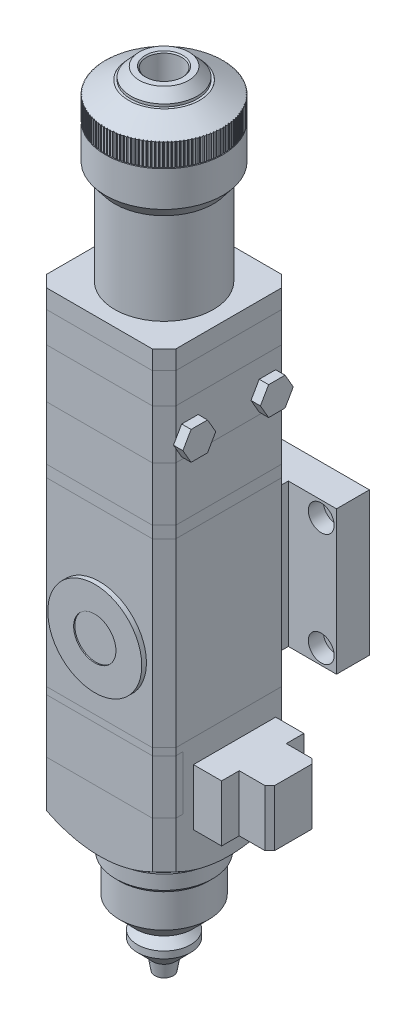
SolidWorks part; units mm, degrees
ref_plane "Front Plane" through (0, 0, 0) normal (0, 0, 1) x (1, 0, 0)
ref_plane "Top Plane" through (0, 0, 0) normal (0, 1, 0) x (1, 0, 0)
ref_plane "Right Plane" through (0, 0, 0) normal (1, 0, 0) x (0, 0, -1)
sketch "Sketch1" plane through (0, 0, 0) normal (0, 1, 0) x (1, 0, 0)
  line L0 (-27.5, 0) -> (27.5, 0) construction
  line L5 (-66.7299, 27.2787) -> (115.2701, 27.2787) construction
  dimension "D1" = 55
sketch "Sketch2" plane through (0, 0, 0) normal (0, 1, 0) x (1, 0, 0)
  line L1 (-27.5, -27.5) -> (27.5, -27.5)
  line L2 (-27.5, -27.5) -> (-27.5, 27.5)
  line L3 (-27.5, 27.5) -> (27.5, 27.5)
  line L4 (27.5, -27.5) -> (27.5, 27.5)
  line L5 (-27.5, -27.5) -> (27.5, 27.5) construction
  line L6 (-27.5, 27.5) -> (27.5, -27.5) construction
  point P0 (0, 0)
  dimension "D1" = 55
sketch "Sketch3" plane through (0, 0, 0) normal (0, 0, 1) x (1, 0, 0)
  line L0 (-51.0962, -28.8167) -> (190.9038, -28.8167) construction
sketch "Sketch33" plane through (0, 0, 0) normal (1, 0, 0) x (0, 0, -1)
  line L0 (-62.9213, -37.0491) -> (115.0787, -37.0491) construction
extrude "Boss-Extrude1" add sketch "Sketch2" against normal blind 8
chamfer "Chamfer1" distance 5 angle 45 4 edges at (27.5, -4, 27.5) (-27.5, -4, -27.5) (-27.5, -4, 27.5) (27.5, -4, -27.5)
sketch "Sketch4" plane through (0, -8, 0) normal (0, -1, 0) x (1, 0, 0)
  line L4 (27.5, -22.5) -> (27.5, 22.5)
  line L5 (22.5, 27.5) -> (-22.5, 27.5)
  line L6 (-27.5, 22.5) -> (-27.5, -22.5)
  line L7 (-22.5, -27.5) -> (22.5, -27.5)
  line L8 (27.5, -22.5) -> (27.5, 22.5)
  line L9 (22.5, 27.5) -> (-22.5, 27.5)
  line L10 (-27.5, 22.5) -> (-27.5, -22.5)
  line L11 (-22.5, -27.5) -> (22.5, -27.5)
  line L16 (-27.5, -22.5) -> (-22.5, -27.5)
  line L17 (-27.5, -22.5) -> (-22.5, -27.5)
  line L18 (22.5, -27.5) -> (27.5, -22.5)
  line L19 (22.5, -27.5) -> (27.5, -22.5)
  line L20 (27.5, 22.5) -> (22.5, 27.5)
  line L21 (27.5, 22.5) -> (22.5, 27.5)
  line L22 (-22.5, 27.5) -> (-27.5, 22.5)
  line L23 (-22.5, 27.5) -> (-27.5, 22.5)
  dimension "D1" = 0
extrude "Boss-Extrude2" add sketch "Sketch4" along normal blind 13 separate body
sketch "Sketch5" plane through (0, -21, 0) normal (0, -1, 0) x (1, 0, 0)
  line L4 (-22.5, -27.5) -> (22.5, -27.5)
  line L5 (27.5, -22.5) -> (27.5, 22.5)
  line L6 (22.5, 27.5) -> (-22.5, 27.5)
  line L7 (-27.5, 22.5) -> (-27.5, -22.5)
  line L8 (-22.5, -27.5) -> (22.5, -27.5)
  line L9 (27.5, -22.5) -> (27.5, 22.5)
  line L10 (22.5, 27.5) -> (-22.5, 27.5)
  line L11 (-27.5, 22.5) -> (-27.5, -22.5)
  line L16 (27.5, 22.5) -> (22.5, 27.5)
  line L17 (27.5, 22.5) -> (22.5, 27.5)
  line L18 (-22.5, 27.5) -> (-27.5, 22.5)
  line L19 (-22.5, 27.5) -> (-27.5, 22.5)
  line L20 (-27.5, -22.5) -> (-22.5, -27.5)
  line L21 (-27.5, -22.5) -> (-22.5, -27.5)
  line L22 (22.5, -27.5) -> (27.5, -22.5)
  line L23 (22.5, -27.5) -> (27.5, -22.5)
  dimension "D1" = 0
extrude "Boss-Extrude3" add sketch "Sketch5" along normal blind 21 separate body
sketch "Sketch6" plane through (0, -42, 0) normal (0, -1, 0) x (1, 0, 0)
  line L4 (-27.5, 22.5) -> (-27.5, -22.5)
  line L5 (-22.5, -27.5) -> (22.5, -27.5)
  line L6 (27.5, -22.5) -> (27.5, 22.5)
  line L7 (22.5, 27.5) -> (-22.5, 27.5)
  line L8 (-27.5, 22.5) -> (-27.5, -22.5)
  line L9 (-22.5, -27.5) -> (22.5, -27.5)
  line L10 (27.5, -22.5) -> (27.5, 22.5)
  line L11 (22.5, 27.5) -> (-22.5, 27.5)
  line L16 (22.5, -27.5) -> (27.5, -22.5)
  line L17 (22.5, -27.5) -> (27.5, -22.5)
  line L18 (27.5, 22.5) -> (22.5, 27.5)
  line L19 (27.5, 22.5) -> (22.5, 27.5)
  line L20 (-22.5, 27.5) -> (-27.5, 22.5)
  line L21 (-22.5, 27.5) -> (-27.5, 22.5)
  line L22 (-27.5, -22.5) -> (-22.5, -27.5)
  line L23 (-27.5, -22.5) -> (-22.5, -27.5)
  dimension "D1" = 0
extrude "Boss-Extrude4" add sketch "Sketch6" along normal blind 23 separate body
sketch "Sketch7" plane through (0, -65, 0) normal (0, -1, 0) x (1, 0, 0)
  line L4 (22.5, 27.5) -> (-22.5, 27.5)
  line L5 (-27.5, 22.5) -> (-27.5, -22.5)
  line L6 (-22.5, -27.5) -> (22.5, -27.5)
  line L7 (27.5, -22.5) -> (27.5, 22.5)
  line L8 (22.5, 27.5) -> (-22.5, 27.5)
  line L9 (-27.5, 22.5) -> (-27.5, -22.5)
  line L10 (-22.5, -27.5) -> (22.5, -27.5)
  line L11 (27.5, -22.5) -> (27.5, 22.5)
  line L16 (-27.5, -22.5) -> (-22.5, -27.5)
  line L17 (-27.5, -22.5) -> (-22.5, -27.5)
  line L18 (22.5, -27.5) -> (27.5, -22.5)
  line L19 (22.5, -27.5) -> (27.5, -22.5)
  line L20 (27.5, 22.5) -> (22.5, 27.5)
  line L21 (27.5, 22.5) -> (22.5, 27.5)
  line L22 (-22.5, 27.5) -> (-27.5, 22.5)
  line L23 (-22.5, 27.5) -> (-27.5, 22.5)
  dimension "D1" = 0
extrude "Boss-Extrude5" add sketch "Sketch7" along normal blind 5 separate body
sketch "Sketch8" plane through (0, -70, 0) normal (0, -1, 0) x (1, 0, 0)
  line L4 (27.5, -22.5) -> (27.5, 22.5)
  line L5 (22.5, 27.5) -> (-22.5, 27.5)
  line L6 (-27.5, 22.5) -> (-27.5, -22.5)
  line L7 (-22.5, -27.5) -> (22.5, -27.5)
  line L8 (27.5, -22.5) -> (27.5, 22.5)
  line L9 (22.5, 27.5) -> (-22.5, 27.5)
  line L10 (-27.5, 22.5) -> (-27.5, -22.5)
  line L11 (-22.5, -27.5) -> (22.5, -27.5)
  line L16 (-22.5, 27.5) -> (-27.5, 22.5)
  line L17 (-22.5, 27.5) -> (-27.5, 22.5)
  line L18 (-27.5, -22.5) -> (-22.5, -27.5)
  line L19 (-27.5, -22.5) -> (-22.5, -27.5)
  line L20 (22.5, -27.5) -> (27.5, -22.5)
  line L21 (22.5, -27.5) -> (27.5, -22.5)
  line L22 (27.5, 22.5) -> (22.5, 27.5)
  line L23 (27.5, 22.5) -> (22.5, 27.5)
  dimension "D1" = 0
extrude "Boss-Extrude6" add sketch "Sketch8" along normal blind 77 separate body
sketch "Sketch9" plane through (0, -147, 0) normal (0, -1, 0) x (1, 0, 0)
  line L4 (-22.5, -27.5) -> (22.5, -27.5)
  line L5 (27.5, -22.5) -> (27.5, 22.5)
  line L6 (22.5, 27.5) -> (-22.5, 27.5)
  line L7 (-27.5, 22.5) -> (-27.5, -22.5)
  line L8 (-22.5, -27.5) -> (22.5, -27.5)
  line L9 (27.5, -22.5) -> (27.5, 22.5)
  line L10 (22.5, 27.5) -> (-22.5, 27.5)
  line L11 (-27.5, 22.5) -> (-27.5, -22.5)
  line L16 (27.5, 22.5) -> (22.5, 27.5)
  line L17 (27.5, 22.5) -> (22.5, 27.5)
  line L18 (-22.5, 27.5) -> (-27.5, 22.5)
  line L19 (-22.5, 27.5) -> (-27.5, 22.5)
  line L20 (-27.5, -22.5) -> (-22.5, -27.5)
  line L21 (-27.5, -22.5) -> (-22.5, -27.5)
  line L22 (22.5, -27.5) -> (27.5, -22.5)
  line L23 (22.5, -27.5) -> (27.5, -22.5)
  dimension "D1" = 0
extrude "Boss-Extrude7" add sketch "Sketch9" along normal blind 10 separate body
sketch "Sketch10" plane through (0, -157, 0) normal (0, -1, 0) x (1, 0, 0)
  line L4 (-27.5, 22.5) -> (-27.5, -22.5)
  line L5 (-22.5, -27.5) -> (22.5, -27.5)
  line L6 (27.5, -22.5) -> (27.5, 22.5)
  line L7 (22.5, 27.5) -> (-22.5, 27.5)
  line L8 (-27.5, 22.5) -> (-27.5, -22.5)
  line L9 (-22.5, -27.5) -> (22.5, -27.5)
  line L10 (27.5, -22.5) -> (27.5, 22.5)
  line L11 (22.5, 27.5) -> (-22.5, 27.5)
  line L16 (22.5, -27.5) -> (27.5, -22.5)
  line L17 (22.5, -27.5) -> (27.5, -22.5)
  line L18 (27.5, 22.5) -> (22.5, 27.5)
  line L19 (27.5, 22.5) -> (22.5, 27.5)
  line L20 (-22.5, 27.5) -> (-27.5, 22.5)
  line L21 (-22.5, 27.5) -> (-27.5, 22.5)
  line L22 (-27.5, -22.5) -> (-22.5, -27.5)
  line L23 (-27.5, -22.5) -> (-22.5, -27.5)
  dimension "D1" = 0
extrude "Boss-Extrude8" add sketch "Sketch10" along normal blind 25 separate body
sketch "Sketch11" plane through (0, -182, 0) normal (0, -1, 0) x (1, 0, 0)
  line L4 (22.5, 27.5) -> (-22.5, 27.5)
  line L5 (-27.5, 22.5) -> (-27.5, -22.5)
  line L6 (-22.5, -27.5) -> (22.5, -27.5)
  line L7 (27.5, -22.5) -> (27.5, 22.5)
  line L8 (22.5, 27.5) -> (-22.5, 27.5)
  line L9 (-27.5, 22.5) -> (-27.5, -22.5)
  line L10 (-22.5, -27.5) -> (22.5, -27.5)
  line L11 (27.5, -22.5) -> (27.5, 22.5)
  line L16 (-27.5, -22.5) -> (-22.5, -27.5)
  line L17 (-27.5, -22.5) -> (-22.5, -27.5)
  line L18 (22.5, -27.5) -> (27.5, -22.5)
  line L19 (22.5, -27.5) -> (27.5, -22.5)
  line L20 (27.5, 22.5) -> (22.5, 27.5)
  line L21 (27.5, 22.5) -> (22.5, 27.5)
  line L22 (-22.5, 27.5) -> (-27.5, 22.5)
  line L23 (-22.5, 27.5) -> (-27.5, 22.5)
  dimension "D1" = 0
extrude "Boss-Extrude9" add sketch "Sketch11" along normal blind 20
sketch "Sketch12" plane through (0, 0, 0) normal (0, 0, 1) x (1, 0, 0)
  line L0 (0, -254) -> (0, -202)
  line L1 (22.5, -202) -> (-22.5, -202) construction
  line L2 (-43, -186) -> (-43, -254)
  line L3 (-43, -254) -> (0, -254)
  line L4 (-20, -202) -> (0, -202)
  arc A1 (-43, -186) -> (-20, -202) centre (7.6658, -137.6991) ccw
  dimension "D1" = 70
  dimension "D2" = 43
  dimension "D3" = 23
  dimension "D4" = 52
  dimension "D5" = 68
revolve "Cut-Revolve1" cut sketch "Sketch12" angle 360 about L0
sketch "Sketch13" plane through (0, 0, 0) normal (0, 0, 1) x (1, 0, 0)
  line L0 (0, -202) -> (0, -254.1474)
  line L1 (-20, -202) -> (20, -202) construction
  line L2 (0, -254.1474) -> (-3.9151, -254.1474)
  line L3 (-3.9151, -254.1474) -> (-4.8686, -248.4385)
  line L4 (-4.8686, -248.4385) -> (-11.3427, -241.864)
  line L5 (-11.3427, -241.864) -> (-11.3427, -238.9532)
  line L6 (-11.3427, -238.9532) -> (-7.5787, -235.9922)
  line L7 (-7.5787, -235.9922) -> (-7.5787, -232.8806)
  line L8 (-7.5787, -232.8806) -> (-12.0955, -232.8806)
  line L9 (-12.0955, -232.8806) -> (-19.049, -225.8194)
  line L10 (-19.049, -225.8194) -> (-19.049, -211.6648)
  line L11 (-19.049, -211.6648) -> (-20.6557, -210.0332)
  line L12 (-20.6557, -210.0332) -> (-20.6557, -204.0238)
  line L13 (-20.6557, -204.0238) -> (-20, -202)
  line L14 (-20, -202) -> (0, -202)
  arc A0 (-27.5, -198.2248) -> (-20, -202) centre (7.6658, -137.6991) ccw construction
  dimension "D1" = 3.9151
  dimension "D2" = 4.8686
  dimension "D3" = 11.3427
  dimension "D4" = 7.5787
  dimension "D5" = 12.0955
  dimension "D6" = 19.049
  dimension "D7" = 20.6557
  dimension "D8" = 52.1474
  dimension "D9" = 2.0238
  dimension "D10" = 8.0332
  dimension "D11" = 9.6648
  dimension "D12" = 23.8194
  dimension "D13" = 33.9922
  dimension "D14" = 36.9532
  dimension "D15" = 39.864
revolve "Revolve1" add sketch "Sketch13" angle 360 about L0
sketch "Sketch14" plane through (0, 0, 0) normal (0, 0, 1) x (1, 0, 0)
  line L0 (0, 0) -> (-20.994, 0)
  line L1 (-27.5, 0) -> (27.5, 0) construction
  line L2 (-20.994, 0) -> (-20.994, 38.9334)
  line L3 (-20.994, 38.9334) -> (-24.972, 44.0621)
  line L4 (-24.972, 44.0621) -> (-24.972, 68.899)
  line L5 (-24.972, 68.899) -> (-15.1506, 74.207)
  line L6 (-15.1506, 74.207) -> (-10.497, 79.2429)
  line L7 (-10.497, 79.2429) -> (0, 79.2429)
  line L8 (0, 79.2429) -> (0, 0)
  dimension "D1" = 79.2429
  dimension "D2" = 20.994
  dimension "D3" = 24.972
  dimension "D4" = 38.9334
  dimension "D5" = 44.0621
  dimension "D6" = 15.1506
  dimension "D7" = 10.497
  dimension "D8" = 74.207
  dimension "D9" = 68.899
revolve "Revolve2" add sketch "Sketch14" angle 360 about L8
ref_plane "Plane1" through (0, 0, -46.9) normal (0, 0, 1) x (1, 0, 0)
sketch "Sketch15" plane through (0, 0, -46.9) normal (0, 0, 1) x (1, 0, 0)
  line L0 (-3.9151, -254.1474) -> (3.9151, -254.1474) construction
  line L1 (-40.5, -80.1474) -> (40.5, -80.1474)
  line L2 (-40.5, -80.1474) -> (-40.5, -141.1474)
  line L3 (-40.5, -141.1474) -> (40.5, -141.1474)
  line L4 (40.5, -80.1474) -> (40.5, -141.1474)
  line L5 (0, -141.1474) -> (0, -254.1474) construction
  dimension "D1" = 81
  dimension "D2" = 61
  dimension "D3" = 113
extrude "Boss-Extrude10" add sketch "Sketch15" along normal blind 14 separate body
sketch "Sketch16" plane through (0, -80.1474, 0) normal (0, 1, 0) x (1, 0, 0)
  line L0 (40.5, 32.9) -> (-40.5, 32.9) construction
  line L1 (-20, 32.9) -> (20, 32.9)
  line L2 (-20, 32.9) -> (-20, 27.5)
  line L3 (-20, 27.5) -> (20, 27.5)
  line L4 (20, 32.9) -> (20, 27.5)
  line L5 (22.5, 27.5) -> (-22.5, 27.5) construction
  line L6 (0, 27.5) -> (0, 46.9) construction
  line L7 (40.5, 46.9) -> (-40.5, 46.9) construction
  dimension "D1" = 40
extrude "Boss-Extrude11" add sketch "Sketch16" against normal up to surface (61 mm away) up to face at (0, -141.1474, -39.9)
hole_wizard "CBORE for M6 Hex Socket Head Cap Screw1" positions "Sketch19" profile "Sketch20" counterbore size "M6" standard "DIN" end condition through all
sketch "Sketch19" plane through (0, 0, -32.9) normal (0, 0, 1) x (1, 0, 0)
  line L1 (-34, -86.7272) -> (34, -86.7272) construction
  line L2 (-34, -86.7272) -> (-34, -134.7272) construction
  line L3 (-34, -134.7272) -> (34, -134.7272) construction
  line L4 (34, -86.7272) -> (34, -134.7272) construction
  line L5 (0, -134.7272) -> (0, -254.1474) construction
  line L6 (-3.9151, -254.1474) -> (3.9151, -254.1474) construction
  point P0 (-34, -86.7272)
  point P2 (-34, -134.7272)
  point P4 (34, -86.7272)
  point P6 (34, -134.7272)
  dimension "D1" = 68
  dimension "D2" = 48
sketch "Sketch20" plane through (-34, -86.7272, -32.9) normal (1, 0, 0) x (0, -1, 0)
  line L0 (0, 0) -> (0, 14)
  line L1 (0, 14) -> (3.2, 14)
  line L3 (3.2, 14) -> (3.2, 6.4)
  line L4 (3.2, 6.4) -> (5.5, 6.4)
  line L5 (5.5, 6.4) -> (5.5, 0)
  line L7 (5.5, 0) -> (0, 0)
  line L11 (0, -6.35) -> (0, 107.95) construction
  dimension "Thru Hole Dia." = 6.4
  dimension "Thru Hole Depth" = 14
  dimension "C'Bore Dia." = 11
  dimension "C'Bore Depth" = 6.4
sketch "Sketch21" plane through (0, 79.2429, 0) normal (0, 1, 0) x (1, 0, 0)
  circle A0 centre (0, 0) radius 7.5
  dimension "D1" = 15
extrude "Cut-Extrude1" cut sketch "Sketch21" against normal blind 64
chamfer "Chamfer2" distance 0.5 angle 45 1 edges at (0, 79.2429, 7.5)
sketch "Sketch22" plane through (0, 79.2429, 0) normal (0, 1, 0) x (1, 0, 0)
  circle A2 centre (0, 0) radius 14.1506
  circle A3 centre (0, 0) radius 15.1506 construction
  circle A4 centre (0, 0) radius 15.1506
  dimension "D1" = 1
extrude "Cut-Extrude2" cut sketch "Sketch22" against normal blind 5.04
sketch "Sketch23" plane through (0, 79.2429, 0) normal (0, 1, 0) x (1, 0, 0)
  line L0 (-0.25, 24.9707) -> (0, 24.672)
  line L1 (0, 24.672) -> (0.25, 24.9707)
  line L2 (0, 24.672) -> (0, 0) construction
  line L3 (0, 24.672) -> (0, 24.972) construction
  circle A0 centre (0, 0) radius 24.972 construction
  arc A1 (0.25, 24.9707) -> (-0.25, 24.9707) centre (0, 0) ccw
  dimension "D1" = 0.3
  dimension "D2" = 0.5
extrude "Cut-Extrude3" cut sketch "Sketch23" against normal blind 20
ref_axis "Axis1" through (0, 15.2429, 0) along (0, 1, 0)
pattern_circular "CirPattern1" count 125 over 360 about axis through (0, 15.2429, 0) along (0, 1, 0) of "Cut-Extrude3"
sketch "Sketch24" plane through (0, 0, 27.5) normal (0, 0, 1) x (1, 0, 0)
  line L0 (0, -117) -> (0, -147) construction
  line L1 (22.5, -147) -> (-22.5, -147) construction
  circle A0 centre (0, -117) radius 20
  dimension "D1" = 40
  dimension "D2" = 30
extrude "Boss-Extrude12" add sketch "Sketch24" along normal blind 2 contours A0
sketch "Sketch25" plane through (0, 0, 29.5) normal (0, 0, 1) x (1, 0, 0)
  circle A0 centre (0, -117) radius 9
  dimension "D1" = 18
extrude "Cut-Extrude4" cut sketch "Sketch25" against normal blind 0.5
sketch "Sketch26" plane through (0, 0, 27.5) normal (0, 0, 1) x (1, 0, 0)
  line L0 (-22.5, -21) -> (-22.5, -8) construction
  line L1 (-22.5, -17.0178) -> (-27.5, -17.0178)
  line L2 (-22.5, -17.0178) -> (-22.5, -32.3892)
  line L3 (-22.5, -32.3892) -> (-27.5, -32.3892)
  line L4 (-27.5, -17.0178) -> (-27.5, -32.3892)
  line L5 (-27.5, -42) -> (-27.5, -21) construction
  line L6 (-27.5, 0) -> (27.5, 0) construction
  dimension "D1" = 17.0178
  dimension "D2" = 15.3714
extrude "Cut-Extrude5" cut sketch "Sketch26" against normal through all
sketch "Sketch27" plane through (0, -32.3892, 0) normal (0, 1, 0) x (1, 0, 0)
  line L4 (-22.5, -27.5) -> (-22.5, 27.5)
  line L5 (-22.5, 27.5) -> (-27.5, 22.5)
  line L6 (-27.5, 22.5) -> (-27.5, -22.5)
  line L7 (-27.5, -22.5) -> (-22.5, -27.5)
  line L8 (-22.5, -27.5) -> (-22.5, 27.5)
  line L9 (-22.5, 27.5) -> (-27.5, 22.5)
  line L10 (-27.5, 22.5) -> (-27.5, -22.5)
  line L11 (-27.5, -22.5) -> (-22.5, -27.5)
  dimension "D1" = 0
extrude "Boss-Extrude13" add sketch "Sketch27" along normal up to surface (15.3714 mm away) separate body up to face at (-25, -17.0178, 0)
sketch "Sketch28" plane through (0, 0, 0) normal (0, 0, 1) x (1, 0, 0)
  line L0 (-27.5, -32.3892) -> (-32, -27.8892)
  line L1 (-32, -27.8892) -> (-32, -10.3892)
  line L2 (-32, -10.3892) -> (-27.5, -10.3892)
  line L3 (-27.5, -17.0178) -> (-27.5, -8) construction
  line L4 (-27.5, -10.3892) -> (-27.5, -32.3892)
  dimension "D1" = 4.5
  dimension "D2" = 45
  dimension "D3" = 22
extrude "Boss-Extrude14" add sketch "Sketch28" along normal mid plane 32
fillet "Fillet1" radius 3 2 edges at (-29.75, -10.3892, -16) (-29.75, -10.3892, 16)
sketch "Sketch29" plane through (0, 0, 27.5) normal (0, 0, 1) x (1, 0, 0)
  line L0 (-27.5, -157) -> (-27.5, -147) construction
  line L1 (-27.5, -150) -> (27.5, -150)
  line L2 (-27.5, -150) -> (-27.5, -173)
  line L3 (-27.5, -173) -> (27.5, -173)
  line L4 (27.5, -150) -> (27.5, -173)
  line L5 (27.5, -192.7807) -> (27.5, -157) construction
  line L6 (22.5, -147) -> (-22.5, -147) construction
  dimension "D1" = 3
  dimension "D2" = 23
extrude "Cut-Extrude6" cut sketch "Sketch29" against normal blind 8
sketch "Sketch30" plane through (0, -173, 0) normal (0, 1, 0) x (1, 0, 0)
  line L6 (27.5, -22.5) -> (27.5, -19.5)
  line L7 (27.5, -19.5) -> (-27.5, -19.5)
  line L8 (-27.5, -19.5) -> (-27.5, -22.5)
  line L9 (-27.5, -22.5) -> (-22.5, -27.5)
  line L10 (-22.5, -27.5) -> (22.5, -27.5)
  line L11 (22.5, -27.5) -> (27.5, -22.5)
  line L12 (27.5, -22.5) -> (27.5, -19.5)
  line L13 (27.5, -19.5) -> (-27.5, -19.5)
  line L14 (-27.5, -19.5) -> (-27.5, -22.5)
  line L15 (-27.5, -22.5) -> (-22.5, -27.5)
  line L16 (-22.5, -27.5) -> (22.5, -27.5)
  line L17 (22.5, -27.5) -> (27.5, -22.5)
  dimension "D1" = 0
extrude "Boss-Extrude15" add sketch "Sketch30" along normal up to surface (23 mm away) separate body up to face at (0, -150, 23.1667)
sketch "Sketch31" plane through (0, -157, 0) normal (0, -1, 0) x (1, 0, 0)
  line L0 (27.5, -22.5) -> (27.5, 19.5) construction
  line L1 (27.5, 15) -> (39.5, 15)
  line L2 (27.5, 15) -> (27.5, -20)
  line L3 (27.5, -20) -> (39.5, -20)
  line L4 (52.5, 7.5) -> (52.5, -12.5)
  line L5 (27.5, -2.5) -> (52.5, -2.5) construction
  line L8 (52.5, 7.5) -> (39.5, 7.5)
  line L9 (39.5, 15) -> (39.5, 7.5)
  line L12 (52.5, -12.5) -> (39.5, -12.5)
  line L13 (39.5, -20) -> (39.5, -12.5)
  dimension "D1" = 25
  dimension "D2" = 35
  dimension "D3" = 2.5
  dimension "D4" = 12
  dimension "D5" = 20
extrude "Boss-Extrude16" add sketch "Sketch31" along normal blind 24
chamfer "Chamfer3" distance 2 angle 45 2 edges at (52.5, -169, -12.5) (52.5, -169, 7.5)
sketch "Sketch34" plane through (27.5, 0, 0) normal (1, 0, 0) x (0, 0, -1)
  line L0 (-16.5, -35) -> (16.5, -35) construction
  line L1 (-9.5, -35) -> (-13, -28.9378)
  line L2 (-13, -28.9378) -> (-20, -28.9378)
  line L3 (-20, -28.9378) -> (-23.5, -35)
  line L4 (-23.5, -35) -> (-20, -41.0622)
  line L5 (-20, -41.0622) -> (-13, -41.0622)
  line L6 (-13, -41.0622) -> (-9.5, -35)
  line L7 (9.5, -35) -> (13, -41.0622)
  line L8 (13, -41.0622) -> (20, -41.0622)
  line L9 (20, -41.0622) -> (23.5, -35)
  line L10 (23.5, -35) -> (20, -28.9378)
  line L11 (20, -28.9378) -> (13, -28.9378)
  line L12 (13, -28.9378) -> (9.5, -35)
  line L13 (0, -35) -> (0, -21) construction
  line L14 (22.5, -21) -> (-22.5, -21) construction
  circle A0 centre (-16.5, -35) radius 6.0622 construction
  circle A1 centre (16.5, -35) radius 6.0622 construction
  dimension "D1" = 33
  dimension "D2" = 7
  dimension "D3" = 14
extrude "Boss-Extrude17" add sketch "Sketch34" along normal blind 4
sketch "Sketch35" plane through (31.5, 0, 0) normal (1, 0, 0) x (0, 0, -1)
  line L0 (-16.5, -28.9378) -> (-16.5, -35) construction
  line L1 (-13, -28.9378) -> (-20, -28.9378) construction
  line L2 (-16.5, -35) -> (-9.5, -35) construction
  line L3 (16.5, -28.9378) -> (16.5, -35) construction
  line L4 (20, -28.9378) -> (13, -28.9378) construction
  line L5 (16.5, -35) -> (23.5, -35) construction
  circle A0 centre (-16.5, -35) radius 5
  circle A1 centre (16.5, -35) radius 5
  dimension "D1" = 10
sketch "Sketch36" plane through (0, 0, 0) normal (0, 0, 1) x (1, 0, 0)
  line L0 (24.972, 59.0429) -> (24.672, 59.2429)
  line L1 (24.972, 44.0621) -> (24.972, 68.899) construction
  line L2 (24.672, 59.2429) -> (24.972, 59.4429)
  line L3 (24.972, 59.4429) -> (24.972, 59.0429)
  line L4 (24.672, 59.2429) -> (24.972, 59.2429) construction
  line L5 (24.767, 59.2429) -> (24.6981, 59.2429) construction
  dimension "D1" = 0.4
  dimension "D2" = 0.3
revolve "Cut-Revolve3" cut sketch "Sketch36" angle 360 about axis through (0, 15.2429, 0) along (0, 1, 0)
